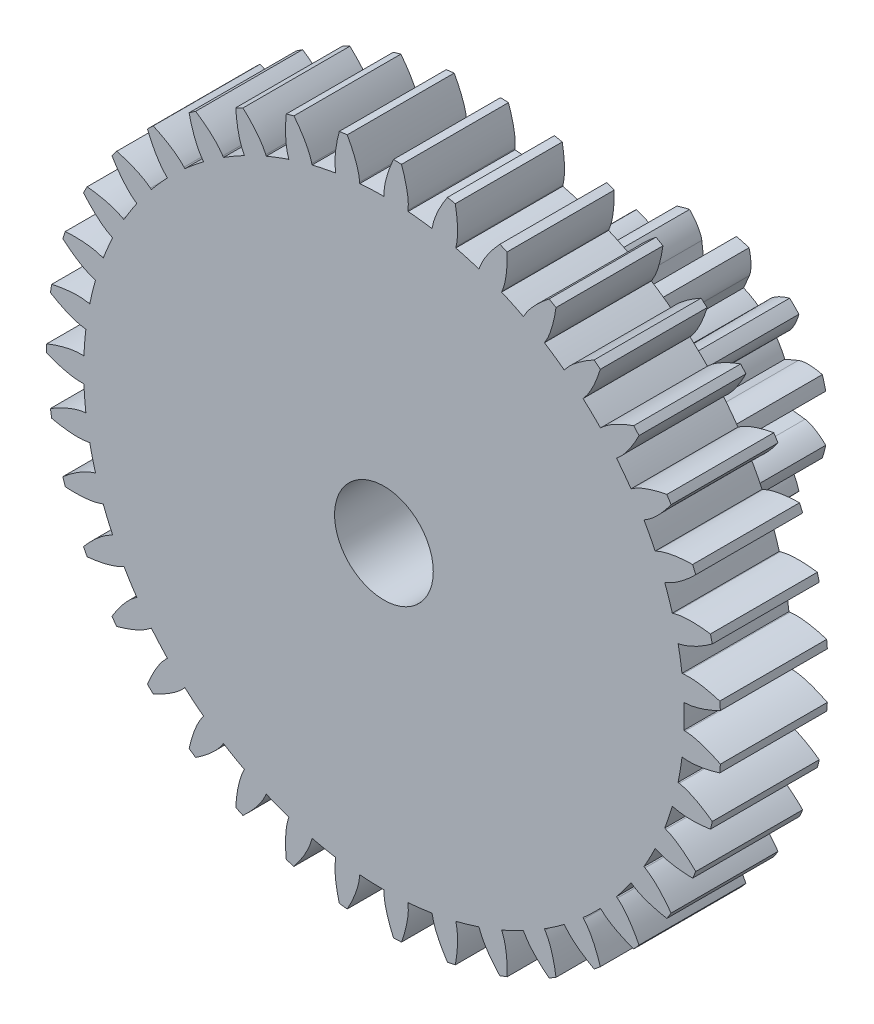
SolidWorks part; units mm, degrees
ref_plane "前视基准面" through (0, 0, 0) normal (0, 0, 1) x (1, 0, 0)
ref_plane "上视基准面" through (0, 0, 0) normal (0, 1, 0) x (1, 0, 0)
ref_plane "右视基准面" through (0, 0, 0) normal (1, 0, 0) x (0, 0, -1)
other "Configuration Table"
sketch "草图1" plane through (0, 0, 0) normal (0, 0, 1) x (1, 0, 0)
  line L0 (0, 0) -> (1.2, 0) construction
  line L1 (0, 0) -> (1.1897, 0.1566) construction
  line L2 (0, 0) -> (1.1195, 0.1354)
  line L3 (1.1897, 0.1566) -> (1.1897, -0.1566) construction
  line L4 (0, 0) -> (1.1195, -0.1354)
  circle A0 centre (0, 0) radius 1.4
  circle A1 centre (0, 0) radius 1.2 construction
  circle A2 centre (0, 0) radius 0.95
  circle A3 centre (0, 0) radius 1.1276 construction
  circle A4 centre (0, 0) radius 0.6
  spline S0 degree 4 poles (1.1195, 0.1354) (1.128, 0.1365) (1.1516, 0.1411) (1.1949, 0.157) (1.2609, 0.1921) (1.3385, 0.2504) (1.4265, 0.3386) (1.513, 0.4563) (1.5884, 0.5979) (1.6479, 0.7602) (1.6868, 0.9286) (1.7064, 1.1002) (1.7082, 1.2814) (1.6868, 1.5048) (1.6275, 1.7661) (1.5147, 2.0566) (1.3415, 2.356) (1.1264, 2.6272) (0.878, 2.867) (0.599, 3.0728) (0.3008, 3.2436) (-0.0211, 3.378) (-0.346, 3.4768) (-0.6967, 3.5387) (-0.9642, 3.5622) (-1.2659, 3.561) (-1.4376, 3.5485) (-1.6326, 3.5286) (-1.737, 3.508) (-1.8243, 3.4941) (-1.8493, 3.4877) (-1.868, 3.4841) knots 0 0 0 0 0 0.005604 0.015718 0.02996 0.048734 0.068727 0.096889 0.125051 0.153212 0.181374 0.209535 0.237696 0.271429 0.327752 0.384075 0.440398 0.496721 0.553044 0.609367 0.66569 0.722013 0.778336 0.834659 0.890982 0.909091 0.954545 0.977273 0.988636 1 1 1 1 1 construction
  spline S1 degree 4 poles (1.1195, 0.1354) (1.128, 0.1365) (1.1516, 0.1411) (1.1949, 0.157) (1.2609, 0.1921) (1.3385, 0.2504) (1.4265, 0.3386) (1.513, 0.4563) (1.5884, 0.5979) (1.6479, 0.7602) (1.6868, 0.9286) (1.7064, 1.1002) (1.7082, 1.2814) (1.6868, 1.5048) (1.6275, 1.7661) (1.5147, 2.0566) (1.3415, 2.356) (1.1264, 2.6272) (0.878, 2.867) (0.599, 3.0728) (0.3008, 3.2436) (-0.0211, 3.378) (-0.346, 3.4768) (-0.6967, 3.5387) (-0.9642, 3.5622) (-1.1881, 3.5613) (-1.292, 3.5571) (-1.3172, 3.5557) knots 0 0 0 0 0 0.005604 0.015718 0.02996 0.048734 0.068727 0.096889 0.125051 0.153212 0.181374 0.209535 0.237696 0.271429 0.327752 0.384075 0.440398 0.496721 0.553044 0.609367 0.66569 0.722013 0.778336 0.834659 0.890982 0.909091 0.909091 0.909091 0.909091 0.909091
  spline S2 degree 4 poles (1.1195, -0.1354) (1.128, -0.1365) (1.1516, -0.1411) (1.1949, -0.157) (1.2609, -0.1921) (1.3385, -0.2504) (1.4265, -0.3386) (1.513, -0.4563) (1.5884, -0.5979) (1.6479, -0.7602) (1.6868, -0.9286) (1.7064, -1.1002) (1.7082, -1.2814) (1.6868, -1.5048) (1.6275, -1.7661) (1.5147, -2.0566) (1.3415, -2.356) (1.1264, -2.6272) (0.878, -2.867) (0.599, -3.0728) (0.3008, -3.2436) (-0.0211, -3.378) (-0.346, -3.4768) (-0.6967, -3.5387) (-0.9642, -3.5622) (-1.2659, -3.561) (-1.4376, -3.5485) (-1.6326, -3.5286) (-1.737, -3.508) (-1.8243, -3.4941) (-1.8493, -3.4877) (-1.868, -3.4841) knots 0 0 0 0 0 0.005604 0.015718 0.02996 0.048734 0.068727 0.096889 0.125051 0.153212 0.181374 0.209535 0.237696 0.271429 0.327752 0.384075 0.440398 0.496721 0.553044 0.609367 0.66569 0.722013 0.778336 0.834659 0.890982 0.909091 0.954545 0.977273 0.988636 1 1 1 1 1 construction
  spline S3 degree 4 poles (1.1195, -0.1354) (1.128, -0.1365) (1.1516, -0.1411) (1.1949, -0.157) (1.2609, -0.1921) (1.3385, -0.2504) (1.4265, -0.3386) (1.513, -0.4563) (1.5884, -0.5979) (1.6479, -0.7602) (1.6868, -0.9286) (1.7064, -1.1002) (1.7082, -1.2814) (1.6868, -1.5048) (1.6275, -1.7661) (1.5147, -2.0566) (1.3415, -2.356) (1.1264, -2.6272) (0.878, -2.867) (0.599, -3.0728) (0.3008, -3.2436) (-0.0211, -3.378) (-0.346, -3.4768) (-0.6967, -3.5387) (-0.9642, -3.5622) (-1.1881, -3.5613) (-1.292, -3.5571) (-1.3172, -3.5557) knots 0 0 0 0 0 0.005604 0.015718 0.02996 0.048734 0.068727 0.096889 0.125051 0.153212 0.181374 0.209535 0.237696 0.271429 0.327752 0.384075 0.440398 0.496721 0.553044 0.609367 0.66569 0.722013 0.778336 0.834659 0.890982 0.909091 0.909091 0.909091 0.909091 0.909091
  point P15 (1.1897, 0)
  dimension "齿顶圆直径" = 2.8
  dimension "分度圆直径" = 2.4
  dimension "齿根圆直径" = 1.9
  dimension "基圆直径" = 2.2553
  dimension "内孔直径" = 1.2
  dimension "渐近线镜像线夹角" = 7.5
extrude "凸台-拉伸1" add sketch "草图1" along normal blind 2.7 contours A0 | A4
extrude "切除-拉伸1" cut sketch "草图1<3>" along normal through all contours A2 S3 A0 S1 region at (1.2063, 0, 0)
sketch "草图1<3>" plane through (0, 0, 0) normal (0, 0, 1) x (1, 0, 0) same geometry as "草图1"
pattern_circular "阵列(圆周)1" count 12 every 30 about axis through (0, 0, 2.7) along (0, 0, 1) of "切除-拉伸1"
sketch "草图2" plane through (0, 0, 2.7) normal (0, 0, 1) x (1, 0, 0)
  line L0 (0, 0) -> (3.9, 0) construction
  line L1 (0, 0) -> (3.6618, 0.1476)
  line L2 (0, 0) -> (3.6618, -0.1476)
  line L3 (3.6618, 0.1476) -> (3.6618, -0.1476) construction
  circle A0 centre (0, 0) radius 3.9 construction
  circle A1 centre (0, 0) radius 3.6648 construction
  circle A2 centre (0, 0) radius 3.65
  circle A3 centre (0, 0) radius 4.1
  circle A4 centre (0, 0) radius 0.6
  spline S0 degree 4 poles (3.6618, -0.1476) (3.6897, -0.1487) (3.7674, -0.1576) (3.9119, -0.1977) (4.1348, -0.2942) (4.4013, -0.463) (4.7093, -0.7258) (5.0201, -1.0848) (5.3014, -1.5238) (5.5949, -2.1619) (5.7801, -2.8411) (5.869, -3.5665) (5.856, -4.4361) (5.7315, -5.2982) (5.4421, -6.2685) (4.9581, -7.2836) (4.3333, -8.2181) (3.5885, -9.0594) (2.7425, -9.7986) (1.8136, -10.4296) (0.8175, -10.9486) (-0.098, -11.3031) (-0.9077, -11.5355) (-1.5224, -11.6672) (-1.9404, -11.7375) (-2.2806, -11.7841) (-2.573, -11.8149) (-2.8026, -11.8357) (-3.064, -11.8509) (-3.329, -11.8626) (-3.5941, -11.8675) (-4.06, -11.8656) (-4.4391, -11.8411) (-4.8329, -11.8129) (-5.0231, -11.7865) (-5.1504, -11.7728) knots 0 0 0 0 0 0.005604 0.015718 0.02996 0.048734 0.068727 0.096889 0.125051 0.153212 0.209535 0.237696 0.271429 0.327752 0.384075 0.440398 0.496721 0.553044 0.609367 0.66569 0.722013 0.778336 0.806497 0.834659 0.84874 0.86282 0.876901 0.890982 0.900036 0.909091 0.931818 0.954545 0.977273 1 1 1 1 1 construction
  spline S1 degree 4 poles (3.6618, -0.1476) (3.6897, -0.1487) (3.7674, -0.1576) (3.9119, -0.1977) (4.1348, -0.2942) (4.4013, -0.463) (4.7093, -0.7258) (5.0201, -1.0848) (5.3014, -1.5238) (5.5949, -2.1619) (5.7801, -2.8411) (5.869, -3.5665) (5.856, -4.4361) (5.7315, -5.2982) (5.4421, -6.2685) (4.9581, -7.2836) (4.3333, -8.2181) (3.5885, -9.0594) (2.7425, -9.7986) (1.8136, -10.4296) (0.8175, -10.9486) (-0.098, -11.3031) (-0.9077, -11.5355) (-1.5224, -11.6672) (-1.9404, -11.7375) (-2.2806, -11.7841) (-2.573, -11.8149) (-2.8026, -11.8357) (-3.064, -11.8509) (-3.2193, -11.8578) (-3.3015, -11.8605) (-3.3424, -11.8617) knots 0 0 0 0 0 0.005604 0.015718 0.02996 0.048734 0.068727 0.096889 0.125051 0.153212 0.209535 0.237696 0.271429 0.327752 0.384075 0.440398 0.496721 0.553044 0.609367 0.66569 0.722013 0.778336 0.806497 0.834659 0.84874 0.86282 0.876901 0.890982 0.900036 0.909091 0.909091 0.909091 0.909091 0.909091
  spline S2 degree 4 poles (3.6618, 0.1476) (3.6897, 0.1487) (3.7674, 0.1576) (3.9119, 0.1977) (4.1348, 0.2942) (4.4013, 0.463) (4.7093, 0.7258) (5.0201, 1.0848) (5.3014, 1.5238) (5.5949, 2.1619) (5.7801, 2.8411) (5.869, 3.5665) (5.856, 4.4361) (5.7315, 5.2982) (5.4421, 6.2685) (4.9581, 7.2836) (4.3333, 8.2181) (3.5885, 9.0594) (2.7425, 9.7986) (1.8136, 10.4296) (0.8175, 10.9486) (-0.098, 11.3031) (-0.9077, 11.5355) (-1.5224, 11.6672) (-1.9404, 11.7375) (-2.2806, 11.7841) (-2.573, 11.8149) (-2.8026, 11.8357) (-3.064, 11.8509) (-3.329, 11.8626) (-3.5941, 11.8675) (-4.06, 11.8656) (-4.4391, 11.8411) (-4.8329, 11.8129) (-5.0231, 11.7865) (-5.1504, 11.7728) knots 0 0 0 0 0 0.005604 0.015718 0.02996 0.048734 0.068727 0.096889 0.125051 0.153212 0.209535 0.237696 0.271429 0.327752 0.384075 0.440398 0.496721 0.553044 0.609367 0.66569 0.722013 0.778336 0.806497 0.834659 0.84874 0.86282 0.876901 0.890982 0.900036 0.909091 0.931818 0.954545 0.977273 1 1 1 1 1 construction
  spline S3 degree 4 poles (3.6618, 0.1476) (3.6897, 0.1487) (3.7674, 0.1576) (3.9119, 0.1977) (4.1348, 0.2942) (4.4013, 0.463) (4.7093, 0.7258) (5.0201, 1.0848) (5.3014, 1.5238) (5.5949, 2.1619) (5.7801, 2.8411) (5.869, 3.5665) (5.856, 4.4361) (5.7315, 5.2982) (5.4421, 6.2685) (4.9581, 7.2836) (4.3333, 8.2181) (3.5885, 9.0594) (2.7425, 9.7986) (1.8136, 10.4296) (0.8175, 10.9486) (-0.098, 11.3031) (-0.9077, 11.5355) (-1.5224, 11.6672) (-1.9404, 11.7375) (-2.2806, 11.7841) (-2.573, 11.8149) (-2.8026, 11.8357) (-3.064, 11.8509) (-3.2193, 11.8578) (-3.3015, 11.8605) (-3.3424, 11.8617) knots 0 0 0 0 0 0.005604 0.015718 0.02996 0.048734 0.068727 0.096889 0.125051 0.153212 0.209535 0.237696 0.271429 0.327752 0.384075 0.440398 0.496721 0.553044 0.609367 0.66569 0.722013 0.778336 0.806497 0.834659 0.84874 0.86282 0.876901 0.890982 0.900036 0.909091 0.909091 0.909091 0.909091 0.909091
  point P16 (3.6618, 0)
  dimension "内孔直径" = 1.2
  dimension "分度圆直径" = 7.8
  dimension "齿顶圆直径" = 8.2
  dimension "基圆直径" = 7.3296
  dimension "齿根圆直径" = 7.3
  dimension "渐开线镜像线夹角" = 2.308
extrude "凸台-拉伸2" add sketch "草图2" along normal blind 1.3 contours A3 | A4
extrude "切除-拉伸3" cut sketch "草图2<3>" along normal through all contours S3 L1 A2 L2 S1 A3 region at (3.8995, 0, 2.7)
sketch "草图2<3>" plane through (0, 0, 2.7) normal (0, 0, 1) x (1, 0, 0) same geometry as "草图2"
pattern_circular "阵列(圆周)2" count 39 over 360 about axis through (0, 0, 4) along (0, 0, 1) of "切除-拉伸3"
equation "\"m\" = 0.2'模数"
equation "\"z\" = 12'齿数"
equation "\"a\"= 20度'压力角"
equation "\"d\"= \"m\" * \"z\"'分度圆直径"
equation "\"da\"= ( \"z\" + 2 ) * \"m\"'齿顶圆直径"
equation "\"df\"= ( \"z\" - 2.5 ) * \"m\"'齿根圆直径"
equation "\"s\"= 0.5 * PI * \"m\"'分度圆齿厚"
equation "\"r\"= 0.38 * \"m\"'齿根圆角"
equation "\"B\"= 0.3 * \"d\"'齿厚"
equation "\"db\"= \"m\" * \"z\" * cos ( \"a\" )'基圆直径"
equation "\"rb\"= \"db\" / 2'基圆半径"
equation "\"齿顶圆直径@草图1\"= \"da\""
equation "\"分度圆直径@草图1\"= \"d\""
equation "\"齿根圆直径@草图1\"= \"df\""
equation "\"基圆直径@草图1\"= \"db\""
equation "\"渐近线镜像线夹角@草图1\"= 360 / 4 / \"z\""
equation "\"h\" = 2.7mm'齿轮厚度"
equation "\"ir\" = 1.2mm'内孔直径"
equation "\"内孔直径@草图1\"= \"ir\""
equation "\"齿轮厚@凸台-拉伸1\"= \"h\""
equation "\"齿轮夹角@阵列(圆周)1\"= 360 / \"z\""
equation "\"齿数@阵列(圆周)1\"= \"z\""
equation "\"m1\" = 0.2'模数"
equation "\"z1\" = 39'齿数"
equation "\"a1\"= 20度'压力角"
equation "\"d1\"= \"m1\" * \"z1\"'分度圆直径"
equation "\"da1\"= ( \"z1\" + 2 ) * \"m1\"'齿顶圆直径"
equation "\"df1\"= ( \"z1\" - 2.5 ) * \"m1\"'齿根圆直径"
equation "\"s1\"= 0.5 * PI * \"m1\"'分度圆齿厚"
equation "\"r1\"= 0.38 * \"m1\"'齿根圆角"
equation "\"B1\"= 0.3 * \"d1\"'齿厚"
equation "\"db1\"= \"m1\" * \"z1\" * cos ( \"a1\" )'基圆直径"
equation "\"rb1\"= \"db1\" / 2'基圆半径"
equation "\"分度圆直径@草图2\"= \"d1\""
equation "\"齿顶圆直径@草图2\"= \"da1\""
equation "\"基圆直径@草图2\"= \"db1\""
equation "\"齿根圆直径@草图2\"= \"df1\""
equation "\"渐开线镜像线夹角@草图2\"= 360 / 4 / \"z1\""
equation "\"内孔直径@草图2\"= \"ir\""
equation "\"二层齿轮厚@凸台-拉伸2\" = \"h1\""
equation "\"h1\"= 1.3'齿轮厚度"
equation "\"二层齿数@阵列(圆周)2\"= \"z1\""
